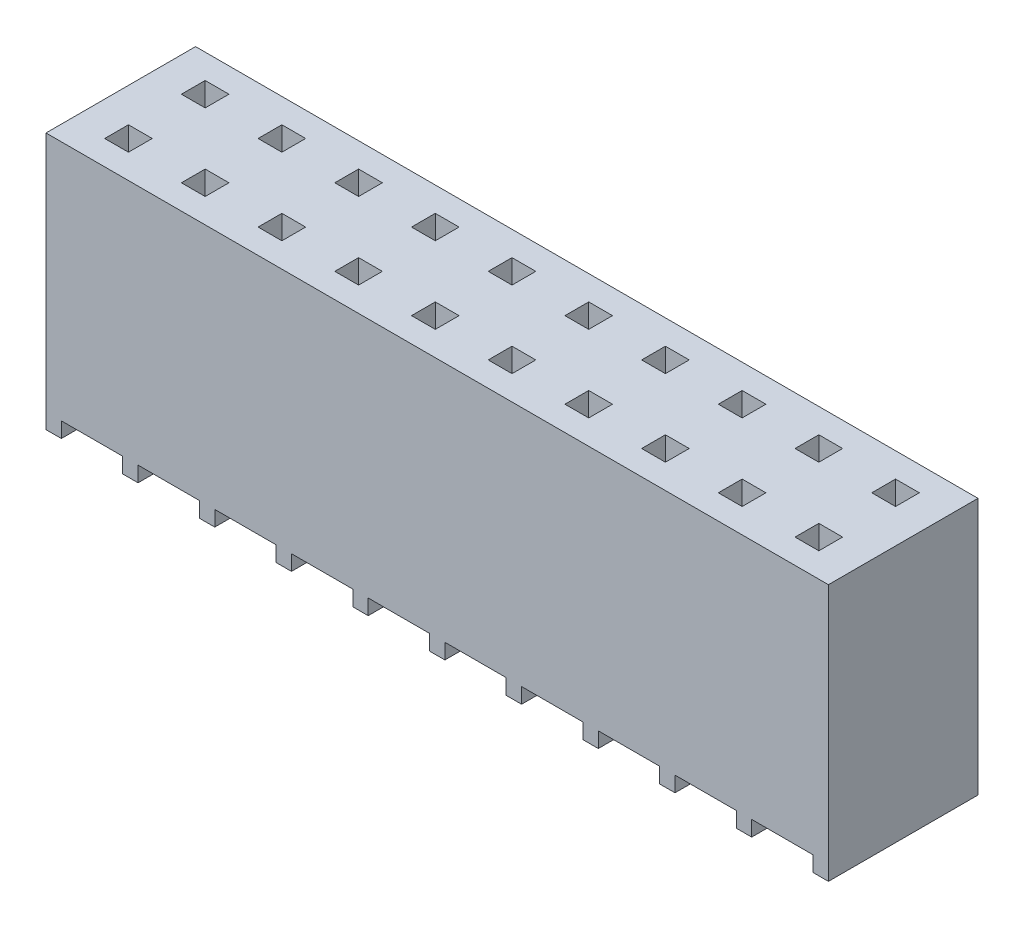
SolidWorks part; units mm, degrees
material "CA"
ref_plane "Front Plane" through (0, 0, 0) normal (0, 0, 1) x (1, 0, 0)
ref_plane "Top Plane" through (0, 0, 0) normal (0, 1, 0) x (1, 0, 0)
ref_plane "Right Plane" through (0, 0, 0) normal (1, 0, 0) x (0, 0, -1)
ref_plane "Plane1" through (0, 0, 2.4765) normal (0, 0, 1) x (1, 0, 0)
sketch "Sketch1" plane through (0, 0, 2.4765) normal (0, 0, 1) x (1, 0, 0)
  line L0 (-12.954, 0.508) -> (12.954, 0.508)
  line L1 (12.954, 0.508) -> (12.954, 8.509)
  line L2 (12.954, 8.509) -> (-12.954, 8.509)
  line L3 (-12.954, 8.509) -> (-12.954, 0.508)
extrude "Boss-Extrude1" add sketch "Sketch1" against normal blind 4.953
sketch "Sketch2" plane through (0, 0.508, 0) normal (0, -1, 0) x (1, 0, 0)
  line L0 (11.0363, -0.8763) -> (11.0363, -1.6637)
  line L1 (11.0363, -1.6637) -> (11.8237, -1.6637)
  line L2 (11.8237, -1.6637) -> (11.8237, -0.8763)
  line L3 (11.8237, -0.8763) -> (11.0363, -0.8763)
extrude "Cut-Extrude1" cut sketch "Sketch2" against normal through all
sketch3d "3DSketch1"
  point P0 (-0.0555, 4.5085, 100.0062)
  point P1 (-0.0555, 4.5085, 0.0062)
ref_axis "Axis1" through (-0.0555, 4.5085, 100.0062) along (0, 0, -1)
pattern_linear "LPattern1" count 2 spacing 2.54 along (0, 0, 1) count 10 spacing 2.54 along (-1, 0, 0) of "Cut-Extrude1"
sketch "Sketch3" plane through (0, 0.508, 0) normal (0, -1, 0) x (1, 0, 0)
  line L0 (-12.446, 2.4765) -> (-12.446, -2.4765)
  line L1 (-12.446, -2.4765) -> (-12.954, -2.4765)
  line L2 (-12.954, -2.4765) -> (-12.954, 2.4765)
  line L3 (-12.954, 2.4765) -> (-12.446, 2.4765)
extrude "Boss-Extrude2" add sketch "Sketch3" along normal blind 0.508
pattern_linear "LPattern2" count 11 spacing 2.54 along (1, 0, 0) of "Boss-Extrude2"
